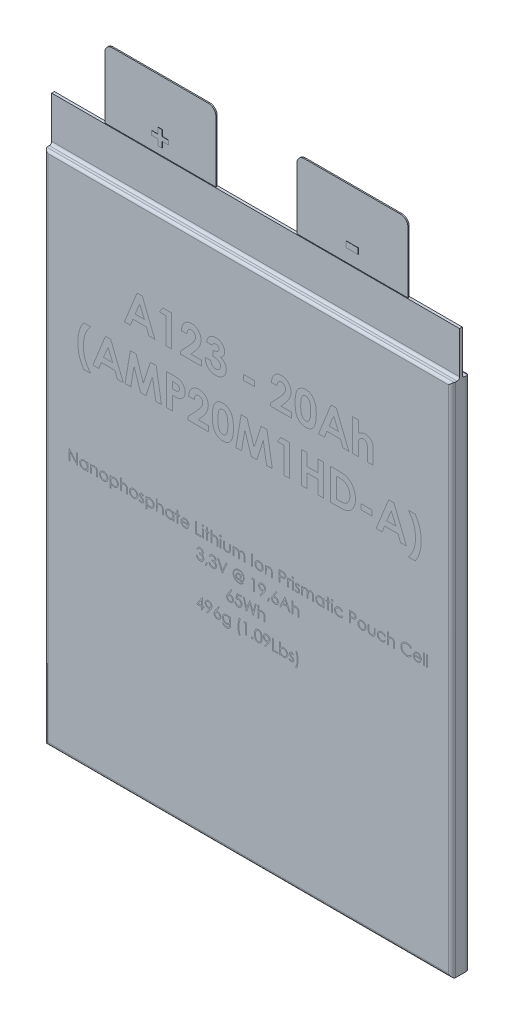
SolidWorks part; units mm, degrees
ref_plane "Face" through (0, 0, 0) normal (0, 0, 1) x (1, 0, 0)
ref_plane "Dessus" through (0, 0, 0) normal (0, 1, 0) x (1, 0, 0)
ref_plane "Droite" through (0, 0, 0) normal (1, 0, 0) x (0, 0, -1)
sketch "Sketch1" plane through (0, 0, 0) normal (0, 0, 1) x (1, 0, 0)
  line L1 (-107.0007, 55.1801) -> (58.9993, 55.1801)
  line L2 (-107.0007, 55.1801) -> (-107.0007, -172.8199)
  line L3 (-107.0007, -172.8199) -> (58.9993, -172.8199)
  line L4 (58.9993, 55.1801) -> (58.9993, -172.8199)
  dimension "D1" = 166
  dimension "D2" = 228
extrude "Boss-Extrude1" add sketch "Sketch1" along normal blind 3.65 and the other way blind 3.65
fillet "Fillet1" radius 1.5 8 edges at (-24.0007, 55.1801, 3.65) (58.9993, -58.8199, 3.65) (-24.0007, -172.8199, 3.65) (-107.0007, -58.8199, 3.65) (-24.0007, -172.8199, -3.65) (58.9993, -58.8199, -3.65) (-24.0007, 55.1801, -3.65) (-107.0007, -58.8199, -3.65)
ref_plane "Mid Plane 1" through (0, 0, 0) normal (0, 0, 1) x (1, 0, 0)
sketch "Sketch2" plane through (0, 0, 0) normal (0, 0, 1) x (1, 0, 0)
  line L0 (-107.0007, 55.1801) -> (58.9993, 55.1801) construction
  line L1 (-24.0007, 55.1801) -> (-24.0007, 65.1801) construction
  line L2 (-7.5007, 65.1801) -> (-7.5007, 55.1801) construction
  line L3 (-40.5007, 55.1801) -> (-85.7007, 55.1801)
  line L4 (-85.7007, 80.1801) -> (-85.7007, 55.1801)
  line L5 (-43.5007, 83.1801) -> (-82.7007, 83.1801)
  line L6 (-40.5007, 80.1801) -> (-40.5007, 55.1801)
  line L7 (-40.5007, 65.1801) -> (-7.5007, 65.1801) construction
  line L8 (-7.5007, 55.1801) -> (37.6993, 55.1801) construction
  line L9 (-4.5007, 83.1801) -> (34.6993, 83.1801) construction
  line L10 (37.6993, 80.1801) -> (37.6993, 55.1801) construction
  line L11 (-7.5007, 80.1801) -> (-7.5007, 55.1801) construction
  arc A0 (-40.5007, 80.1801) -> (-43.5007, 83.1801) centre (-43.5007, 80.1801) ccw
  arc A1 (-82.7007, 83.1801) -> (-85.7007, 80.1801) centre (-82.7007, 80.1801) ccw
  arc A2 (37.6993, 80.1801) -> (34.6993, 83.1801) centre (34.6993, 80.1801) ccw construction
  arc A3 (-4.5007, 83.1801) -> (-7.5007, 80.1801) centre (-4.5007, 80.1801) ccw construction
  point P19 (-40.5007, 83.1801)
  point P22 (-85.7007, 83.1801)
  point P25 (37.6993, 83.1801)
  point P28 (-7.5007, 83.1801)
  point P30 (-24.0007, 65.1801)
  dimension "D4" = 3
  dimension "D5" = 3
  dimension "D1" = 166
  dimension "D2" = 10
  dimension "D3" = 33
  dimension "D6" = 28
  dimension "D7" = 45.2
extrude "Boss-Extrude2" add sketch "Sketch2" along normal blind 0.25 and the other way blind 0.25
ref_plane "Mid Plane 2" through (0, 0, 0) normal (0, 0, 1) x (1, 0, 0)
sketch "Sketch3" plane through (0, 0, 0) normal (0, 0, 1) x (1, 0, 0)
  line L0 (-7.5007, 55.1801) -> (37.6993, 55.1801)
  line L1 (37.6993, 55.1801) -> (37.6993, 80.1801)
  line L2 (34.6993, 83.1801) -> (-4.5007, 83.1801)
  line L3 (-7.5007, 80.1801) -> (-7.5007, 55.1801)
  arc A0 (37.6993, 80.1801) -> (34.6993, 83.1801) centre (34.6993, 80.1801) ccw
  arc A1 (-4.5007, 83.1801) -> (-7.5007, 80.1801) centre (-4.5007, 80.1801) ccw
  point P11 (37.6993, 83.1801)
  point P14 (-7.5007, 83.1801)
  dimension "D1" = 3
extrude "Boss-Extrude3" add sketch "Sketch3" along normal blind 0.25 and the other way blind 0.25
sketch "Sketch7" plane through (0, 0, -3.65) normal (0, 0, -1) x (-1, 0, 0)
  line L0 (107.0007, 55.1801) -> (107.0007, -172.8199) construction
  line L1 (-58.9993, 55.1801) -> (107.0007, 55.1801)
  line L2 (-58.9993, 55.1801) -> (-58.9993, 37.1801)
  line L3 (-58.9993, 37.1801) -> (107.0007, 37.1801)
  line L4 (107.0007, 55.1801) -> (107.0007, 37.1801)
  dimension "D1" = 18
extrude "Cut-Extrude1" cut sketch "Sketch7" against normal blind 3.1
mirror "Mirror2" about plane through (0, 0, 0) normal (0, 0, 1) of "Cut-Extrude1"
ref_plane "Plane3" through (0, 0, 0.25) normal (0, 0, 1) x (1, 0, 0)
sketch "Sketch4" plane through (0, 0, 0.25) normal (0, 0, 1) x (1, 0, 0)
  line L0 (-85.7007, 67.6801) -> (-47.0007, 67.6801) construction
  line L1 (-85.7007, 80.1801) -> (-85.7007, 55.1801) construction
  line L2 (37.6993, 55.1801) -> (37.6993, 80.1801) construction
  line L3 (-7.5007, 56.4788) -> (37.6993, 56.4788) construction
  line L4 (-85.7007, 56.4788) -> (-40.5007, 56.4788) construction
  line L5 (-7.0007, 67.6801) -> (37.6993, 67.6801) construction
  line L6 (-40.5007, 55.1801) -> (-40.5007, 80.1801) construction
  line L7 (-7.5007, 80.1801) -> (-7.5007, 55.1801) construction
  text T0 "+" font "Century Gothic" height 10
  text T1 "-" font "Century Gothic" height 14
extrude "Boss-Extrude4" add sketch "Sketch4" along normal blind 0.1
ref_plane "MidPlane 3" through (0, 0, 0) normal (0, 0, 1) x (1, 0, 0)
mirror "Mirror1" about plane through (0, 0, 0) normal (0, 0, 1) of "Boss-Extrude4"
ref_plane "Plane4" through (0, 0, 8.65) normal (0, 0, 1) x (1, 0, 0)
sketch "Sketch5" plane through (0, 0, 8.65) normal (0, 0, 1) x (1, 0, 0)
  line L0 (-107.0007, -67.8199) -> (58.9993, -67.8199) construction
  line L1 (-107.0007, -172.8199) -> (-107.0007, 37.1801) construction
  line L2 (58.9993, 37.1801) -> (58.9993, -172.8199) construction
  line L3 (-24.0007, 55.1801) -> (-24.0007, -172.8199) construction
  line L5 (58.9993, -172.8199) -> (-107.0007, -172.8199) construction
  line L6 (-105.5007, -7.5199) -> (58.9993, -7.5199) construction
  line L7 (58.9993, 37.1801) -> (58.9993, -172.8199) construction
  line L8 (-105.5007, 37.1801) -> (-105.5007, -171.3199) construction
  text T0 "A123 - 20Ah\r\n(AMP20M1HD-A)" font "Century Gothic" height 12.7
wrap "Wrap1" sketch "Sketch5" wrap type scribe source sketch "Sketch5" face at (-24.0007, -67.0699, 3.65)
ref_plane "Plane5" through (0, 0, 13.65) normal (0, 0, 1) x (1, 0, 0)
sketch "Sketch6" plane through (0, 0, 13.65) normal (0, 0, 1) x (1, 0, 0)
  line L0 (-107.0007, -67.8199) -> (58.9993, -67.8199) construction
  text T0 "Nanophosphate Lithium Ion Prismatic Pouch Cell\r\n3,3V @ 19,6Ah\r\n65Wh \r\n496g (1.09Lbs)" font "Century Gothic" height 4.5
wrap "Wrap2" sketch "Sketch6" wrap type scribe source sketch "Sketch6" face at (-24.0007, -67.0699, 3.65)
ref_plane "Plane6" through (0, 0, 0) normal (0, 0, 1) x (1, 0, 0)
ref_plane "Plane7" through (0, -44.8199, 0) normal (0, -1, 0) x (-1, 0, 0)
ref_plane "Plane8" through (-24.0007, 0, 0) normal (-1, 0, 0) x (0, 0, 1)
sketch "bounding_box" plane through (0, 0, 0) normal (0, 0, 1) x (1, 0, 0)
  line L0 (-105.5007, 47.9786) -> (57.4993, 47.9786) construction
  line L5 (-105.5007, 37.1801) -> (-105.5007, -171.3199) construction
  line L6 (57.4993, -171.3199) -> (57.4993, 37.1801) construction
  line L7 (-24.0007, 47.9786) -> (-24.0007, -191.8118) construction
  line L9 (-100.4228, 55.1801) -> (-100.4228, -172.8199) construction
  line L11 (58.9993, -172.8199) -> (-107.0007, -172.8199) construction
  line L12 (-100.1918, -58.8199) -> (83.0974, -58.8199) construction
  line L13 (-86.4007, 55.6801) -> (-86.4007, 84.6801)
  line L14 (59.9993, -173.3199) -> (-108.0007, -173.3199)
  line L15 (59.9993, -173.3199) -> (59.9993, 55.6801)
  line L16 (59.9993, 55.6801) -> (38.3993, 55.6801)
  line L17 (-108.0007, -173.3199) -> (-108.0007, 55.6801)
  line L18 (59.9993, -173.3199) -> (-108.0007, 55.6801) construction
  line L19 (59.9993, 55.6801) -> (-108.0007, -173.3199) construction
  line L20 (-86.4007, 84.6801) -> (-39.9007, 84.6801)
  line L21 (-39.9007, 84.6801) -> (-39.9007, 55.6801)
  line L22 (-8.1007, 55.6801) -> (-8.1007, 84.6801)
  line L23 (-8.1007, 84.6801) -> (38.3993, 84.6801)
  line L24 (38.3993, 84.6801) -> (38.3993, 55.6801)
  line L25 (-86.4007, 55.6801) -> (-108.0007, 55.6801)
  line L26 (-8.1007, 55.6801) -> (-39.9007, 55.6801)
  point P15 (-24.0007, -58.8199)
  point P19 (-24.0007, 47.9786)
  point P20 (-100.4228, -58.8199)
  point P21 (-24.0007, -58.8199)
  point P33 (-24.0007, 55.6801)
  dimension "D1" = 168
  dimension "D2" = 229
  dimension "D3" = 29
  dimension "D4" = 46.5
  dimension "D5" = 31.8
fillet "Fillet2" radius 1 4 edges at (-24.0007, 37.1801, -3.65) (-24.0007, 37.1801, -0.55) (-24.0007, 37.1801, 0.55) (-24.0007, 37.1801, 3.65) tangent propagation no
